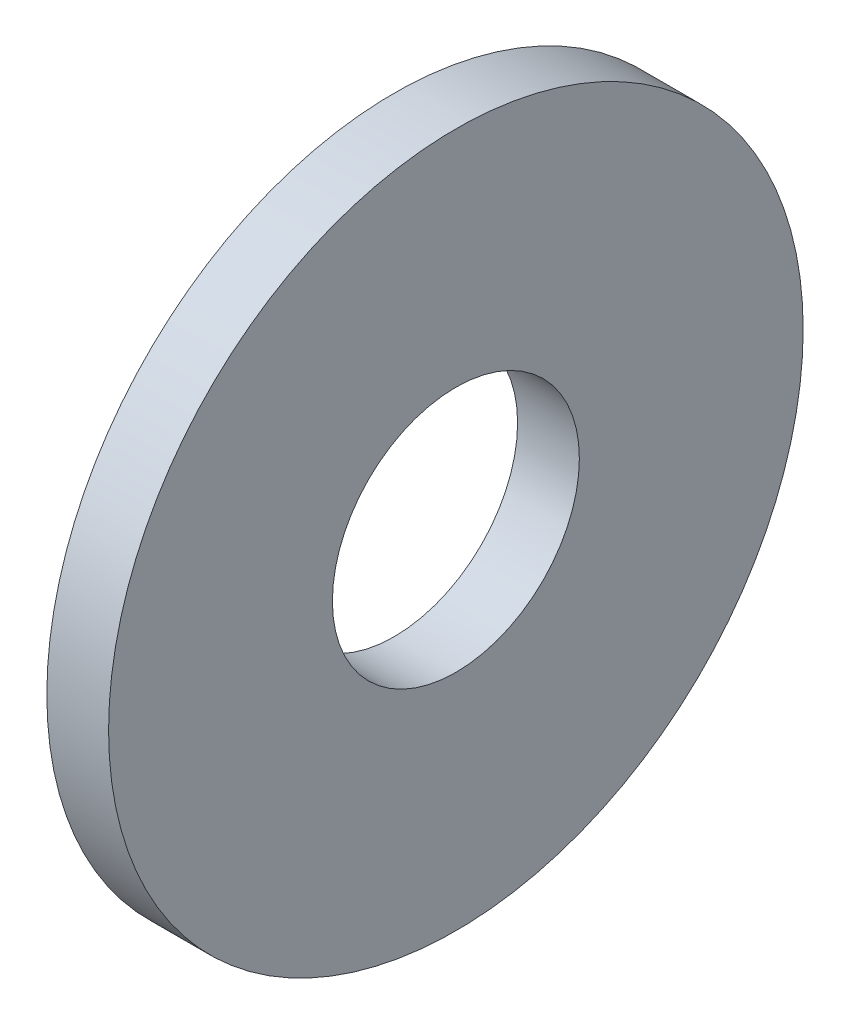
SolidWorks part; units mm, degrees
material "ASTM A36 Steel"
ref_plane "Front Plane" through (0, 0, 0) normal (0, 0, 1) x (1, 0, 0)
ref_plane "Top Plane" through (0, 0, 0) normal (0, 1, 0) x (1, 0, 0)
ref_plane "Right Plane" through (0, 0, 0) normal (1, 0, 0) x (0, 0, -1)
other "Configuration Table"
sketch "Sketch_Washer_Profile" plane through (0, 0, 0) normal (0, 0, 1) x (1, 0, 0)
  line L0 (-5, 0) -> (5, 0) construction
  line L2 (0, 3.2) -> (1.6, 3.2)
  line L3 (0, 3.2) -> (0, 9)
  line L4 (0, 9) -> (1.6, 9)
  line L5 (1.6, 3.2) -> (1.6, 9)
revolve "Washer_Revolve_ID6p4_OD18_T1p6" add sketch "Sketch_Washer_Profile" angle 360 about L0
ref_axis "Shaft_Axis_X" through (106.7263, 0, 0) along (-1, 0, 0)
